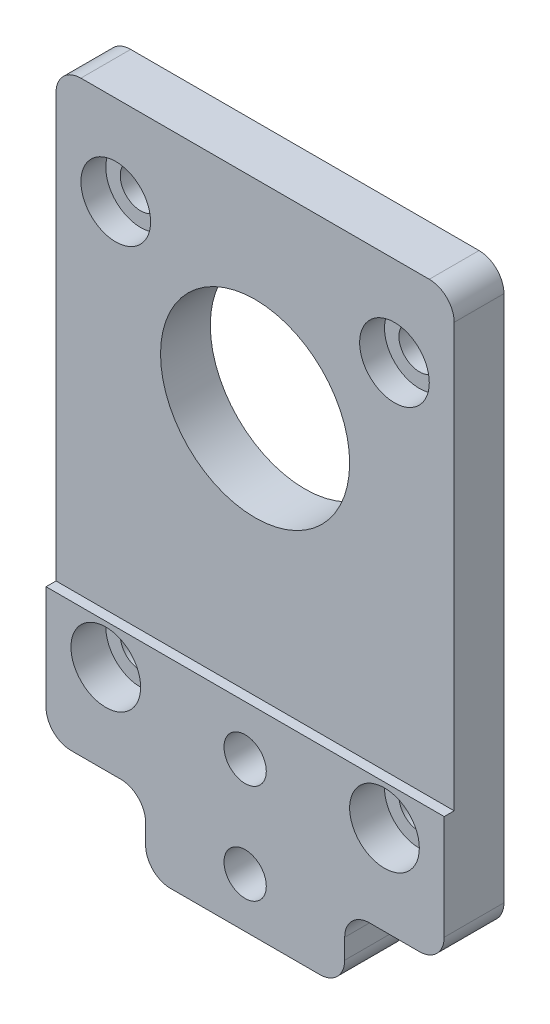
SolidWorks part; units mm, degrees
ref_plane "Front Plane" through (0, 0, 0) normal (0, 0, 1) x (1, 0, 0)
ref_plane "Top Plane" through (0, 0, 0) normal (0, 1, 0) x (1, 0, 0)
ref_plane "Right Plane" through (0, 0, 0) normal (1, 0, 0) x (0, 0, -1)
sketch "Sketch1" plane through (0, 0, 0) normal (0, 0, 1) x (1, 0, 0)
  line L0 (0, -353.8104) -> (0, 17336.7087) construction
  line L1 (-10, -15) -> (-10, 15)
  line L2 (-10, 15) -> (-15, 30)
  line L3 (10, -15) -> (-10, -15)
  line L4 (10, -15) -> (10, 15)
  line L5 (10, 15) -> (15, 30)
  arc A0 (15, 30) -> (-15, 30) centre (0, 30) ccw
  circle A1 centre (0, 0) radius 2.125
  circle A2 centre (0, -10) radius 2.125
  dimension "D1" = 4.25
  dimension "D2" = 4.25
  dimension "D3" = 10
  dimension "D4" = 30
  dimension "D5" = 30
  dimension "D7" = 30
  dimension "D6" = 5
  dimension "D8" = 20
  dimension "D9" = 10
  dimension "D10" = 30
extrude "Boss-Extrude2" add sketch "Sketch1" along normal blind 6
sketch "Sketch7" plane through (0, 0, 0) normal (0, 0, -1) x (-1, 0, 0)
  line L0 (0, -970) -> (0, 49030) construction
  line L1 (-20, 50) -> (20, 50)
  line L2 (-20, 50) -> (-20, -8)
  line L3 (-20, -8) -> (20, -8)
  line L4 (20, 50) -> (20, -8)
  arc A0 (15, 30) -> (-15, 30) centre (0, 30) ccw construction
  dimension "D1" = 40
  dimension "D2" = 58
  dimension "D3" = 20
  dimension "D4" = 20
extrude "Boss-Extrude3" add sketch "Sketch7" against normal blind 6
fillet "Fillet1" radius 2.5 8 edges at (10, -15, 3) (-10, -15, 3) (20, 50, 3) (10, -8, 3) (20, -8, 3) (-20, 50, 3) (-20, -8, 3) (-10, -8, 3)
sketch "Sketch3" plane through (0, 0, 6) normal (0, 0, 1) x (1, 0, 0)
  circle A0 centre (0, 30) radius 9.5
  dimension "D1" = 19
  dimension "D2" = 30
extrude "Cut-Extrude2" cut sketch "Sketch3" against normal through all
sketch "Sketch2" plane through (0, 0, 6) normal (0, 0, 1) x (1, 0, 0)
  line L0 (-1009.4328, 41) -> (48990.5672, 41) construction
  line L1 (-1007.6541, 1) -> (48992.3459, 1) construction
  line L2 (-14, -973.06) -> (-14, 49026.94) construction
  line L3 (14, -977.0128) -> (14, 49022.9872) construction
  line L4 (0, -970) -> (0, 49030) construction
  line L5 (-1000, 30) -> (49000, 30) construction
  line L6 (-17.5, 50) -> (17.5, 50) construction
  circle A0 centre (-14, 41) radius 2.05
  circle A1 centre (14, 41) radius 2.05
  circle A2 centre (14, 1) radius 2.05
  circle A3 centre (-14, 1) radius 2.05
  dimension "D3" = 9
  dimension "D4" = 40
  dimension "D5" = 4.1
  dimension "D6" = 4.1
  dimension "D7" = 4.1
  dimension "D8" = 4.1
  dimension "D1" = 14
  dimension "D2" = 14
extrude "Cut-Extrude1" cut sketch "Sketch2" against normal through all
sketch "Sketch6" plane through (0, 0, 6) normal (0, 0, 1) x (1, 0, 0)
  line L0 (-7.5, -15) -> (7.5, -15) construction
  line L1 (-30, 5) -> (30, 5)
  line L2 (-30, 5) -> (-30, 55)
  line L3 (-30, 55) -> (30, 55)
  line L4 (30, 5) -> (30, 55)
  line L5 (-30, 5) -> (30, 55) construction
  line L6 (-30, 55) -> (30, 5) construction
  point P0 (0, 30)
  dimension "D1" = 20
  dimension "D2" = 60
extrude "Cut-Extrude5" cut sketch "Sketch6" against normal blind 1
sketch "Sketch9" plane through (0, 0, 6) normal (0, 0, 1) x (1, 0, 0)
  circle A0 centre (0, -10) radius 2.125
  circle A1 centre (0, 0) radius 2.125
  dimension "D1" = 4.25
  dimension "D2" = 4.25
extrude "Cut-Extrude7" cut sketch "Sketch9" against normal through all
sketch "Sketch11" plane through (0, 0, 6) normal (0, 0, 1) x (1, 0, 0)
  circle A0 centre (-14, 1) radius 3.5
  circle A1 centre (14, 1) radius 3.5
  circle A2 centre (14, 41) radius 3.5
  circle A3 centre (-14, 41) radius 3.5
  dimension "D1" = 7
  dimension "D2" = 7
  dimension "D3" = 7
  dimension "D4" = 7
extrude "Cut-Extrude9" cut sketch "Sketch11" against normal blind 3.5
